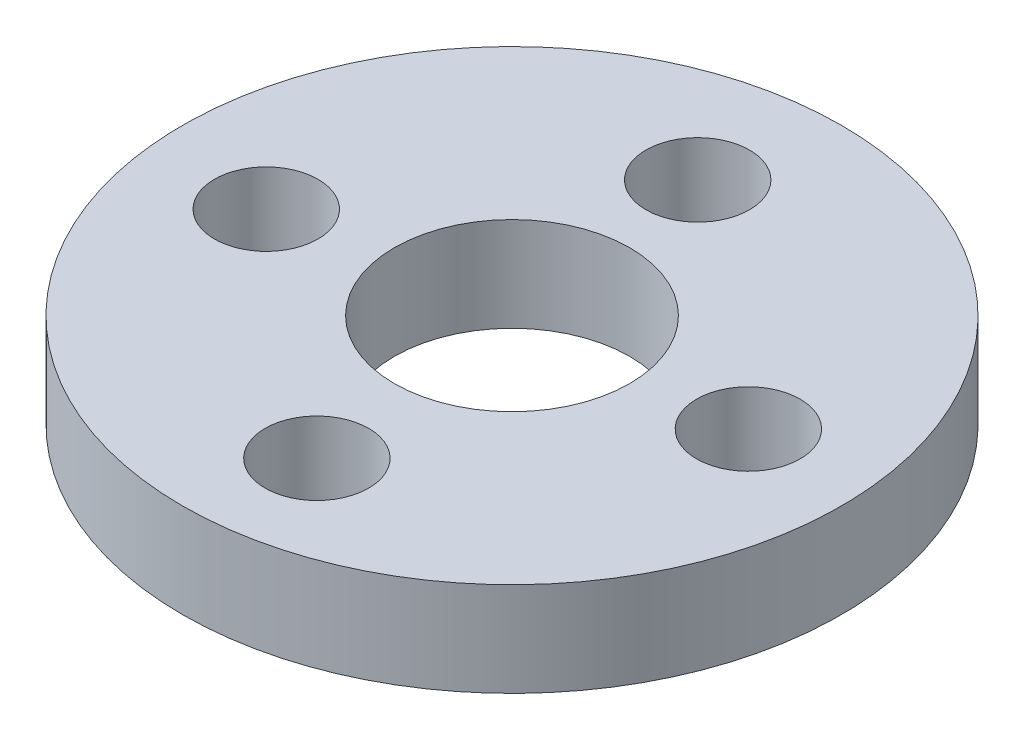
SolidWorks part; units mm, degrees
ref_plane "前视基准面" through (0, 0, 0) normal (0, 0, 1) x (1, 0, 0)
ref_plane "上视基准面" through (0, 0, 0) normal (0, 1, 0) x (1, 0, 0)
ref_plane "右视基准面" through (0, 0, 0) normal (1, 0, 0) x (0, 0, -1)
sketch "草图1" plane through (0, 0, 0) normal (0, 1, 0) x (1, 0, 0)
  circle A0 centre (0, 0) radius 7
extrude "凸台-拉伸1" add sketch "草图1" along normal blind 2
sketch "草图2" plane through (0, 2, 0) normal (0, 1, 0) x (1, 0, 0)
  circle A0 centre (-0.5247, 4.4693) radius 1.1
extrude "切除-拉伸1" cut sketch "草图2" against normal blind 2
ref_point "点1"
ref_plane "基准面1" through (0.0133, 2, 0.1132) normal (0.9932, 0, -0.1166) x (-0.1166, 0, -0.9932)
ref_plane "基准面2" through (0.0133, 0, 0.1132) normal (0.1166, 0, 0.9932) x (0.9932, 0, -0.1166)
mirror "镜向1" about plane through (0.0133, 0, 0.1132) normal (0.1166, 0, 0.9932) of "切除-拉伸1"
ref_axis "基准轴1" through (-7.7, 0, 1.0187) along (0.9932, 0, -0.1166)
ref_axis "基准轴2" through (-0.6215, 2, -5.2944) along (0.1166, 0, 0.9932)
ref_axis "基准轴3" through (0.0133, 7.4447, 0.1132) along (0, -1, 0)
pattern_circular "阵列(圆周)1" count 2 every 90 about axis through (0.0133, 7.4447, 0.1132) along (0, -1, 0) of "镜向1", "切除-拉伸1"
sketch "草图3" plane through (0, 2, 0) normal (0, 1, 0) x (1, 0, 0)
  circle A0 centre (0, 0) radius 2.5
extrude "切除-拉伸2" cut sketch "草图3" against normal blind 2
